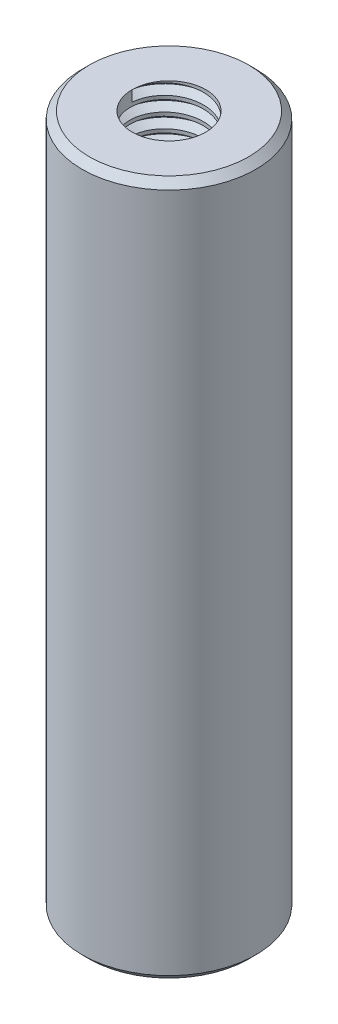
SolidWorks part; units mm, degrees
material "6061-T6 (SS)"
ref_plane "Alzado" through (0, 0, 0) normal (0, 0, 1) x (1, 0, 0)
ref_plane "Planta" through (0, 0, 0) normal (0, 1, 0) x (1, 0, 0)
ref_plane "Vista lateral" through (0, 0, 0) normal (1, 0, 0) x (0, 0, -1)
sketch "Croquis2" plane through (0, 0, 0) normal (0, 1, 0) x (1, 0, 0)
  circle A0 centre (0, 0) radius 4.7625
  dimension "D1" = 9.525
extrude "Saliente-Extruir1" add sketch "Croquis2" along normal mid plane 38.1
chamfer "Chaflán1" distance 0.3969 angle 45 2 edges at (0, -19.05, 4.7625) (0, 19.05, 4.7625)
sketch "Croquis3" plane through (0, 0, 0) normal (0, 1, 0) x (1, 0, 0)
  circle A0 centre (0, 0) radius 2.0193
  dimension "D1" = 4.0386
extrude "Tap Hole 1" cut sketch "Croquis3" against normal blind 12.7 from surface starting at face at (0, 19.05, 4.3656)
extrude "Tap Hole 2" cut sketch "Croquis3<2>" along normal blind 12.7 from surface starting at face at (0, -19.05, 4.3656)
sketch "Croquis3<2>" plane through (0, 0, 0) normal (0, 1, 0) x (1, 0, 0) same geometry as "Croquis3"
sketch "Croquis4" plane through (0, 0, 0) normal (0, 1, 0) x (1, 0, 0)
  circle A0 centre (0, 0) radius 2.4892
  dimension "D1" = 4.9784
extrude "Clearance Hole" [suppressed] cut sketch "Croquis4" against normal through all both and the other way through all
thread "Rosca1" pitch 0.7937 method cut profile "Perfil de rosca1" start angle 0, offset 0, length 0, pitch 0.7937, diameter 4.0386
ref_plane "Plano1" through (-2.0193, 19.05, 0) normal (0, 0, 1) x (-1, 0, 0)
sketch "Perfil de rosca1" plane through (-2.0193, 19.05, 0) normal (0, 0, 1) x (-1, 0, 0)
  line L0 (0, 0) -> (0, 0.7937) construction
  line L1 (0, 0) -> (0.4296, 0.248)
  line L2 (0.4296, 0.248) -> (0.4296, 0.3473)
  line L3 (0.4296, 0.3473) -> (0, 0.5953)
  line L4 (0.4296, 0.2977) -> (0, 0.2977) construction
  line L11 (0, 0) -> (0, 0.5953)
  point P2 (0, 0)
  dimension "Pitch" = 0.7937
  dimension "Profile_Angle" = 60
  dimension "Profile_Land" = 0.0992
  dimension "Profile_Height" = 0.4296
thread "Rosca2" pitch 0.7937 method cut profile "Perfil de rosca2" start angle 0, offset 0, length 0, pitch 0.7937, diameter 4.0386
ref_plane "Plano2" through (2.0193, -19.05, 0) normal (0, 0, 1) x (1, 0, 0)
sketch "Perfil de rosca2" plane through (2.0193, -19.05, 0) normal (0, 0, 1) x (1, 0, 0)
  line L0 (0, 0) -> (0, 0.7937) construction
  line L1 (0, 0) -> (0.4296, 0.248)
  line L2 (0.4296, 0.248) -> (0.4296, 0.3473)
  line L3 (0.4296, 0.3473) -> (0, 0.5953)
  line L4 (0.4296, 0.2977) -> (0, 0.2977) construction
  line L11 (0, 0) -> (0, 0.5953)
  point P2 (0, 0)
  dimension "Pitch" = 0.7937
  dimension "Profile_Angle" = 60
  dimension "Profile_Land" = 0.0992
  dimension "Profile_Height" = 0.4296
equation "\"OD\"= 0.375pulgadas"
equation "\"Largo\"= 1.5pulgadas"
equation "\"Tap Hole\"= IIF ( \"OD\" = 0.375pulgadas , 0.1590pulgadas , 0.201pulgadas )"
equation "\"Spacer Hole\"= IIF ( \"OD\" = 0.375pulgadas , 0.196pulgadas , 0.257pulgadas )"
equation "\"D1@Croquis2\"=\"OD\""
equation "\"D1@Saliente-Extruir1\"=\"Largo\""
equation "\"D1@Croquis3\"=\"Tap Hole\""
equation "\"D1@Croquis4\"=\"Spacer Hole\""
